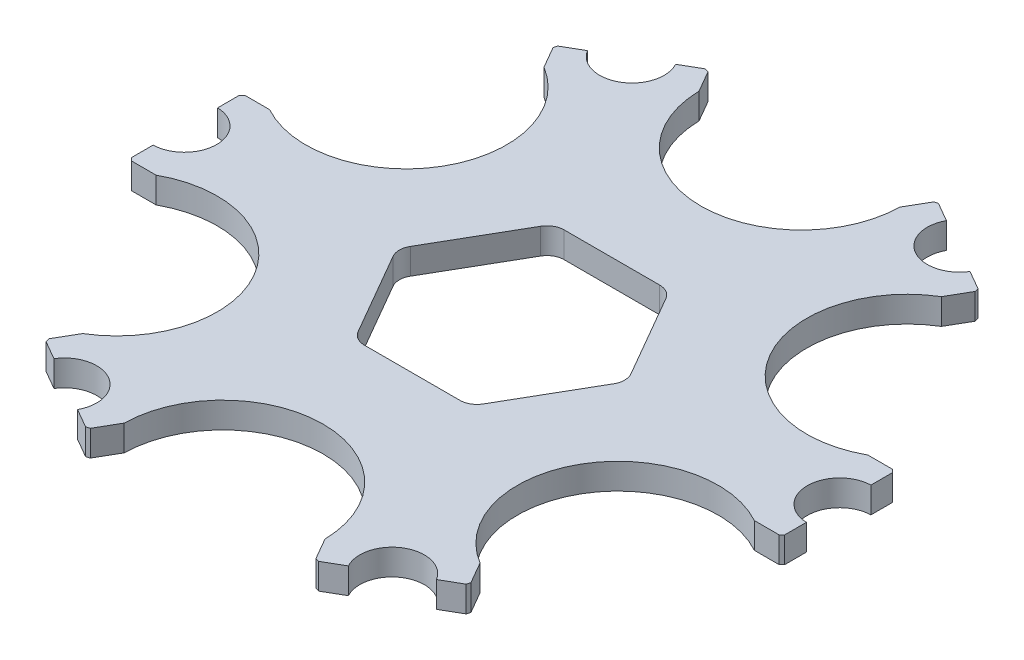
SolidWorks part; units mm, degrees
material "6061-T6 (SS)"
ref_plane "Front Plane" through (0, 0, 0) normal (0, 0, 1) x (1, 0, 0)
ref_plane "Top Plane" through (0, 0, 0) normal (0, 1, 0) x (1, 0, 0)
ref_plane "Right Plane" through (0, 0, 0) normal (1, 0, 0) x (0, 0, -1)
sketch "Sketch1" plane through (0, 0, 0) normal (0, 1, 0) x (1, 0, 0)
  line L0 (0, 0) -> (-62.5623, 0) construction
  line L1 (10.6319, 18.415) -> (-10.6319, 18.415)
  line L2 (-10.6319, 18.415) -> (-21.2638, 0)
  line L3 (-21.2638, 0) -> (-10.6319, -18.415)
  line L4 (-10.6319, -18.415) -> (10.6319, -18.415)
  line L5 (10.6319, -18.415) -> (21.2638, 0)
  line L6 (21.2638, 0) -> (10.6319, 18.415)
  line L7 (-60.2361, 10.4648) -> (-60.2361, 5.9505)
  line L8 (-60.4139, 0) -> (-60.4139, -29.149) construction
  line L9 (-60.2361, -5.9505) -> (-60.2361, -10.4648)
  line L10 (-35.2713, 49.1908) -> (-39.1808, 46.9336)
  line L11 (-21.0553, 57.3984) -> (-24.9648, 55.1412)
  line L12 (24.9648, 55.1412) -> (21.0553, 57.3984)
  line L13 (39.1808, 46.9336) -> (35.2713, 49.1908)
  line L14 (60.2361, 5.9505) -> (60.2361, 10.4648)
  line L15 (60.2361, -10.4648) -> (60.2361, -5.9505)
  line L16 (35.2713, -49.1908) -> (39.1808, -46.9336)
  line L17 (21.0553, -57.3984) -> (24.9648, -55.1412)
  line L18 (-24.9648, -55.1412) -> (-21.0553, -57.3984)
  line L19 (-39.1808, -46.9336) -> (-35.2713, -49.1908)
  line L20 (-60.2361, 10.4648) -> (-55.1561, 10.4648)
  line L21 (-39.1808, 46.9336) -> (-36.6408, 42.5342)
  line L22 (-21.0553, 57.3984) -> (-18.5153, 52.999)
  line L23 (21.0553, 57.3984) -> (18.5153, 52.999)
  line L24 (39.1808, 46.9336) -> (36.6408, 42.5342)
  line L25 (60.2361, 10.4648) -> (55.1561, 10.4648)
  line L26 (60.2361, -10.4648) -> (55.1561, -10.4648)
  line L27 (39.1808, -46.9336) -> (36.6408, -42.5342)
  line L28 (21.0553, -57.3984) -> (18.5153, -52.999)
  line L29 (-21.0553, -57.3984) -> (-18.5153, -52.999)
  line L30 (-39.1808, -46.9336) -> (-36.6408, -42.5342)
  line L31 (-60.2361, -10.4648) -> (-55.1561, -10.4648)
  line L32 (21.0553, 57.3984) -> (18.5153, 52.999)
  line L33 (-21.0553, 57.3984) -> (-18.5153, 52.999)
  line L34 (60.2361, 10.4648) -> (55.1561, 10.4648)
  line L35 (39.1808, 46.9336) -> (36.6408, 42.5342)
  line L36 (39.1808, -46.9336) -> (36.6408, -42.5342)
  line L37 (60.2361, -10.4648) -> (55.1561, -10.4648)
  line L38 (-21.0553, -57.3984) -> (-18.5153, -52.999)
  line L39 (21.0553, -57.3984) -> (18.5153, -52.999)
  line L40 (-60.2361, -10.4648) -> (-55.1561, -10.4648)
  line L41 (-39.1808, -46.9336) -> (-36.6408, -42.5342)
  circle A0 centre (0, 0) radius 18.415 construction
  arc A2 (-60.4139, 5.9531) -> (-60.4139, -5.9531) centre (-60.4139, 0) ccw construction
  arc A8 (-60.2361, 5.9505) -> (-60.2361, -5.9505) centre (-60.4139, 0) cw
  arc A9 (-60.2361, -5.9505) -> (-60.2361, 5.9505) centre (-60.4139, 0) ccw construction
  arc A10 (-24.9648, 55.1412) -> (-35.2713, 49.1908) centre (-30.207, 52.32) cw
  arc A11 (35.2713, 49.1908) -> (24.9648, 55.1412) centre (30.2069, 52.32) cw
  arc A12 (60.2361, -5.9505) -> (60.2361, 5.9505) centre (60.4139, 0) cw
  arc A13 (24.9648, -55.1412) -> (35.2713, -49.1908) centre (30.207, -52.32) cw
  arc A14 (-35.2713, -49.1908) -> (-24.9648, -55.1412) centre (-30.2069, -52.32) cw
  arc A27 (-55.1561, 10.4648) -> (-36.6408, 42.5342) centre (-46.1938, 26.67) ccw
  arc A28 (-18.5153, 52.999) -> (18.5153, 52.999) centre (0, 53.34) ccw
  arc A29 (36.6408, 42.5342) -> (55.1561, 10.4648) centre (46.1938, 26.67) ccw
  arc A30 (55.1561, -10.4648) -> (36.6408, -42.5342) centre (46.1938, -26.67) ccw
  arc A31 (18.5153, -52.999) -> (-18.5153, -52.999) centre (0, -53.34) ccw
  arc A32 (-36.6408, -42.5342) -> (-55.1561, -10.4648) centre (-46.1938, -26.67) ccw
  point P27 (0, 0)
  point P58 (0, 0)
  point P74 (0, 0)
  point P87 (0, 0)
  point P98 (0, 0)
  dimension "D1" = 11.9062
  dimension "D10" = 6
  dimension "D2" = 60.4139
  dimension "D3" = 36.83
  dimension "D6" = 0.3556
  dimension "D7" = 20.9296
  dimension "D9" = 5.08
  dimension "D11" = 53.34
  dimension "D8" = 6
  dimension "D12" = 6
extrude "Boss-Extrude1" add sketch "Sketch1" along normal blind 4.7625 contours L18 L17 A13 L16 L15 A12 L14 L13 A11 L12 L11 A10 L10 L7 A8 L9 L19 A14 L3 L2 L1 L6 L5 L4 region at (-57.6961, 0, -8.8007)
chamfer "Chamfer1" distance 0.508 angle 45 12 edges at (-60.2361, 2.3813, 10.4648) (-39.1808, 2.3813, 46.9336) (-21.0553, 2.3813, 57.3984) (21.0553, 2.3813, 57.3984) (39.1808, 2.3813, 46.9336) (60.2361, 2.3813, 10.4648) (60.2361, 2.3813, -10.4648) (39.1808, 2.3813, -46.9336) (21.0553, 2.3813, -57.3984) (-21.0553, 2.3813, -57.3984) (-39.1808, 2.3813, -46.9336) (-60.2361, 2.3813, -10.4648)
sketch "Sketch3" plane through (0, 0, 0) normal (0, 0, 1) x (1, 0, 0)
  line L0 (0, 32.7405) -> (0, -26.7673) construction
ref_axis "Axis1" through (0, 32.7405, 0) along (0, -1, 0)
fillet "Fillet1" radius 3.175 6 edges at (-21.2638, 2.3813, 0) (-10.6319, 2.3813, 18.415) (10.6319, 2.3813, 18.415) (21.2638, 2.3813, 0) (10.6319, 2.3813, -18.415) (-10.6319, 2.3813, -18.415)
